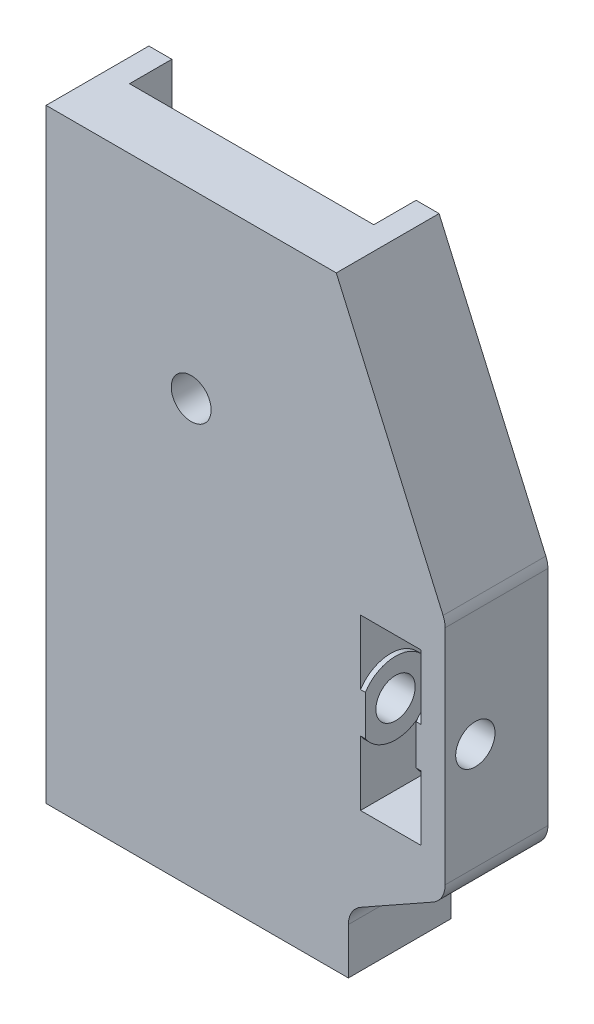
SolidWorks part; units mm, degrees
material "ABS"
ref_plane "前视基准面" through (0, 0, 0) normal (0, 0, 1) x (1, 0, 0)
ref_plane "上视基准面" through (0, 0, 0) normal (0, 1, 0) x (1, 0, 0)
ref_plane "右视基准面" through (0, 0, 0) normal (1, 0, 0) x (0, 0, -1)
other "Configuration Table"
sketch "草图1" plane through (0, 0, 0) normal (0, 0, 1) x (1, 0, 0)
  line L0 (33, 29.5) -> (24, 50)
  line L1 (24, 50) -> (0, 50)
  line L2 (0, 50) -> (0, 0)
  line L5 (33, 9.5) -> (33, 29.5)
  line L6 (26, 12.5) -> (31, 12.5)
  line L7 (26, 26.5) -> (26, 12.5)
  line L12 (31, 26.5) -> (26, 26.5)
  line L17 (31, 12.5) -> (31, 26.5)
  line L18 (0, 0) -> (25, 0)
  line L20 (25, 0) -> (33, 9.5) construction
  line L24 (0, 0) -> (25, 0)
  line L25 (33, 9.5) -> (33, 29.5)
  line L26 (33, 29.5) -> (24, 50)
  line L27 (33, 9.5) -> (25, 5)
  line L28 (25, 5) -> (25, 0)
  circle A0 centre (12, 35) radius 1.65
  dimension "D5" = 3.3
  dimension "D6" = 12
  dimension "D7" = 15
  dimension "D2" = 50
  dimension "D3" = 90
  dimension "D4" = 9.5
  dimension "D8" = 23.5
  dimension "D9" = 26
  dimension "D10" = 5
  dimension "D11" = 14
  dimension "D12" = 25
  dimension "D13" = 33
  dimension "D14" = 4.5
  dimension "D15" = 20
  dimension "D16" = 24
  dimension "D17" = 5
extrude "凸台-拉伸1" add sketch "草图1" against normal blind 8.5 contours L18 L20 L5 L0 L1 L2 A0 L17 L6 L7 L12 region at (14.5327, 24.8991, 0)
sketch "草图2" plane through (0, 50, 0) normal (0, 1, 0) x (1, 0, 0)
  line L0 (24, 8.5) -> (0, 8.5) construction
  line L1 (1.9, 8.5) -> (22.1, 8.5)
  line L2 (1.9, 8.5) -> (1.9, 5)
  line L3 (1.9, 5) -> (22.1, 5)
  line L4 (22.1, 8.5) -> (22.1, 5)
  line L5 (0, 8.5) -> (0, 0) construction
  dimension "D1" = 1.9
  dimension "D2" = 20.2
  dimension "D3" = 3.5
extrude "切除-拉伸1" cut sketch "草图2" against normal through all
sketch "草图3" plane through (33, 0, 0) normal (1, 0, 0) x (0, 0, -1)
  line L0 (0, 9.5) -> (0, 29.5) construction
  circle A0 centre (2.5, 19.5) radius 1.625
  dimension "D1" = 3.25
  dimension "D2" = 2.5
  dimension "D3" = 7
extrude "切除-拉伸2" cut sketch "草图3" against normal up to surface (7 mm away) up to face at (26, 19.5, -4.25)
sketch "草图4" plane through (26, 0, 0) normal (1, 0, 0) x (0, 0, -1)
  circle A0 centre (2.5, 19.5) radius 1
  dimension "D1" = 2
extrude "切除-拉伸3" cut sketch "草图4" against normal up to surface (3.9 mm away) up to face at (22.1, 25, -6.75)
sketch "草图5" plane through (26, 0, 0) normal (1, 0, 0) x (0, 0, -1)
  line L0 (0, 26.5) -> (0, 12.5) construction
  line L1 (0, 21.1583) -> (0, 17.8417)
  arc A0 (0, 17.8417) -> (0, 21.1583) centre (2.5, 19.5) ccw
  circle A2 centre (2.5, 19.5) radius 1 construction
  circle A3 centre (2.5, 19.5) radius 1
  dimension "D1" = 6
extrude "凸台-拉伸2" add sketch "草图5" along normal blind 0.4
sketch "草图6" plane through (31, 0, 0) normal (-1, 0, 0) x (0, 0, 1)
  line L0 (0, 12.5) -> (0, 26.5) construction
  line L1 (0, 17.8417) -> (0, 21.1583)
  circle A0 centre (-2.5, 19.5) radius 1.625 construction
  circle A1 centre (-2.5, 19.5) radius 1.625
  arc A2 (0, 21.1583) -> (0, 17.8417) centre (-2.5, 19.5) ccw
  dimension "D1" = 6
extrude "凸台-拉伸3" add sketch "草图6" along normal blind 0.4
fillet "圆角1" radius 2 3 edges at (33, 29.5, -4.25) (25, 5, -4.25) (33, 9.5, -4.25)
sketch "草图7" plane through (33, 0, 0) normal (1, 0, 0) x (0, 0, -1)
  circle A0 centre (2.5, 19.5) radius 1.625 construction
  circle A1 centre (2.5, 19.5) radius 1.625
extrude "切除-拉伸4" cut sketch "草图7" against normal through all
sketch "草图8" plane through (0, 0, -8.5) normal (0, 0, -1) x (-1, 0, 0)
  line L1 (-31, 12.5) -> (-26, 12.5)
  line L2 (-31, 12.5) -> (-31, 3.563)
  line L3 (-31, 3.563) -> (-26, 3.563)
  line L4 (-26, 12.5) -> (-26, 3.563)
extrude "切除-拉伸5" cut sketch "草图8" against normal blind 2
fillet "圆角2" radius 0.5 2 edges at (31, 8.375, -7.5) (26, 5.5624, -7.5)
fillet "圆角3" radius 1 4 edges at (25.9472, 5.6067, -6.5) (31.2476, 8.7983, -6.5) (26, 9.1652, -6.5) (31, 10.865, -6.5)
